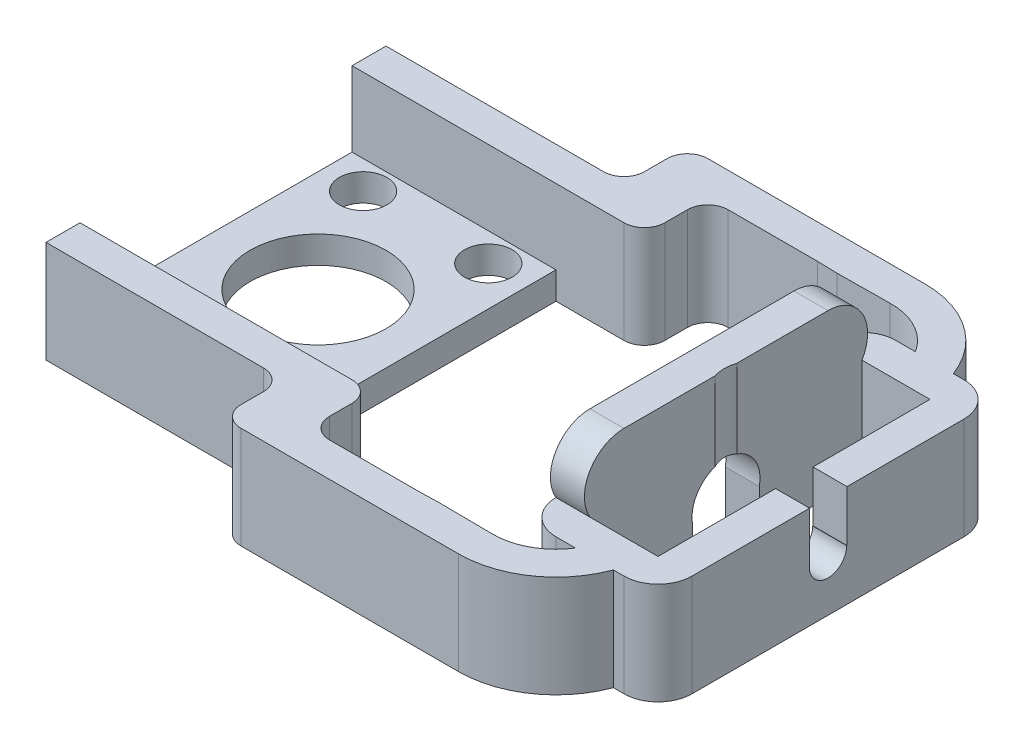
SolidWorks part; units mm, degrees
ref_plane "Front Plane" through (0, 0, 0) normal (0, 0, 1) x (1, 0, 0)
ref_plane "Top Plane" through (0, 0, 0) normal (0, 1, 0) x (1, 0, 0)
ref_plane "Right Plane" through (0, 0, 0) normal (1, 0, 0) x (0, 0, -1)
sketch "Sketch1" plane through (0, 0, 0) normal (0, 1, 0) x (1, 0, 0)
  line L11 (-45, 25) -> (45, 25)
  line L12 (-45, 25) -> (-45, -25)
  line L13 (-45, -25) -> (45, -25)
  line L14 (45, 25) -> (45, -25)
  line L15 (-45, 25) -> (45, -25) construction
  line L16 (-45, -25) -> (45, 25) construction
  point P0 (0, 0)
  dimension "D1" = 50
  dimension "D2" = 90
extrude "Boss-Extrude1" add sketch "Sketch1" along normal blind 15
sketch "Sketch2" plane through (0, 15, 0) normal (0, 1, 0) x (1, 0, 0)
  line L0 (45, -25) -> (45, 25) construction
  line L1 (-15, 20) -> (25, 20)
  line L2 (-15, 20) -> (-15, -20)
  line L3 (-15, -20) -> (25, -20)
  line L4 (25, 20) -> (25, -20)
  line L5 (-15, 20) -> (25, -20) construction
  line L6 (-15, -20) -> (25, 20) construction
  line L7 (30, 20) -> (40, 20)
  line L8 (30, 20) -> (30, -20)
  line L9 (30, -20) -> (40, -20)
  line L10 (40, 20) -> (40, -20)
  line L11 (30, 20) -> (40, -20) construction
  line L12 (30, -20) -> (40, 20) construction
  point P0 (5, 0)
  point P5 (35, 0)
  dimension "D1" = 5
  dimension "D2" = 5
  dimension "D4" = 10
  dimension "D5" = 40
extrude "Cut-Extrude1" cut sketch "Sketch2" against normal blind 15
sketch "Sketch5" plane through (45, 0, 0) normal (1, 0, 0) x (0, 0, -1)
  line L0 (0, 0) -> (0, 15) construction
  line L1 (-25, 0) -> (25, 0) construction
  line L2 (-25, 15) -> (25, 15) construction
  circle A0 centre (-9.038, 7.6891) radius 1.5
  circle A1 centre (9.038, 7.6891) radius 1.5
  point P8 (0, 7.5)
  dimension "D1" = 9.04
sketch "Sketch6" plane through (45, 0, 0) normal (1, 0, 0) x (0, 0, -1)
  line L0 (0, 0) -> (0, 15) construction
  line L1 (-25, 0) -> (25, 0) construction
  line L2 (-25, 15) -> (25, 15) construction
  circle A0 centre (0, 7.5) radius 2.75
  dimension "D1" = 5.5
extrude "Cut-Extrude4" cut sketch "Sketch6" against normal blind 7
sketch "Sketch8" plane through (25, 0, 0) normal (-1, 0, 0) x (0, 0, 1)
  line L0 (0, 0) -> (0, 15) construction
  line L1 (20, 0) -> (-20, 0) construction
  line L2 (20, 15) -> (-20, 15) construction
  circle A0 centre (0, 7.5) radius 5
  dimension "D1" = 10
extrude "Cut-Extrude5" cut sketch "Sketch8" against normal blind 7
sketch "Sketch9" plane through (45, 0, 0) normal (1, 0, 0) x (0, 0, -1)
  line L0 (0, 0) -> (0, 15) construction
  line L1 (-25, 0) -> (25, 0) construction
  line L2 (0, 7.5) -> (-9.04, 7.5) construction
  circle A0 centre (-9.04, 7.5) radius 1.5
  circle A1 centre (9.04, 7.5) radius 1.5
  dimension "D1" = 9.04
sketch "Sketch10" plane through (0, 15, 0) normal (0, 1, 0) x (1, 0, 0)
  line L0 (0, 0) -> (45, 0) construction
  line L1 (45, -25) -> (45, 25) construction
  line L2 (45, 25) -> (-45, 25) construction
  line L3 (11.5635, 25) -> (17.139, 25)
  line L4 (32.861, 25) -> (38.4365, 25)
  line L5 (11.5635, -25) -> (17.139, -25)
  line L6 (32.861, -25) -> (38.4365, -25)
  arc A0 (25, 34.3366) -> (38.4365, 25) centre (25, 20) cw
  arc A1 (25, 34.3366) -> (11.5635, 25) centre (25, 20) ccw
  arc A2 (25, 29.3164) -> (32.861, 25) centre (25, 20) cw
  arc A3 (25, 29.3164) -> (17.139, 25) centre (25, 20) ccw
  arc A4 (25, -29.3164) -> (17.139, -25) centre (25, -20) cw
  arc A5 (25, -29.3164) -> (32.861, -25) centre (25, -20) ccw
  arc A6 (25, -34.3366) -> (38.4365, -25) centre (25, -20) ccw
  arc A7 (25, -34.3366) -> (11.5635, -25) centre (25, -20) cw
extrude "Boss-Extrude2" add sketch "Sketch10" against normal blind 15
sketch "Sketch11" plane through (0, 15, 0) normal (0, 1, 0) x (1, 0, 0)
  line L0 (25, 20) -> (25, 25)
  line L1 (32.861, 25) -> (17.139, 25) construction
  line L2 (25, 25) -> (17.139, 25)
  line L3 (17.139, 25) -> (17.139, 20)
  line L4 (25, 20) -> (-15, 20) construction
  line L5 (17.139, 20) -> (25, 20)
  line L6 (0, 0) -> (30, 0) construction
  line L7 (30, 20) -> (30, -20) construction
  line L8 (17.139, -20) -> (25, -20)
  line L9 (25, -20) -> (25, -25)
  line L10 (25, -25) -> (17.139, -25)
  line L11 (17.139, -25) -> (17.139, -20)
extrude "Cut-Extrude7" cut sketch "Sketch11" against normal blind 15
fillet "Fillet1" radius 5 2 edges at (25, 7.5, -25) (25, 7.5, 25)
fillet "Fillet2" radius 5 2 edges at (17.139, 7.5, 20) (17.139, 7.5, -20)
fillet "Fillet3" radius 5 2 edges at (17.139, 7.5, 25) (17.139, 7.5, -25)
fillet "Fillet4" radius 5 2 edges at (45, 7.5, 25) (45, 7.5, -25)
fillet "Fillet5" radius 5 2 edges at (11.5635, 7.5, -25) (11.5635, 7.5, 25)
sketch "Sketch12" plane through (0, 15, 0) normal (0, 1, 0) x (1, 0, 0)
  line L1 (38.8459, 2.7908) -> (45.6477, 2.7908)
  line L2 (38.8459, 2.7908) -> (38.8459, -2.7092)
  line L3 (38.8459, -2.7092) -> (45.6477, -2.7092)
  line L4 (45.6477, 2.7908) -> (45.6477, -2.7092)
  line L5 (38.8459, 2.7908) -> (45.6477, -2.7092) construction
  line L6 (38.8459, -2.7092) -> (45.6477, 2.7908) construction
  point P0 (42.2468, 0.0408)
  dimension "D1" = 5.5
extrude "Cut-Extrude8" cut sketch "Sketch12" against normal blind 7.5
sketch "Sketch13" plane through (0, 0, 0) normal (0, -1, 0) x (1, 0, 0)
  line L1 (23.6838, 4.8946) -> (31.331, 4.8946)
  line L2 (23.6838, 4.8946) -> (23.6838, -4.8946)
  line L3 (23.6838, -4.8946) -> (31.331, -4.8946)
  line L4 (31.331, 4.8946) -> (31.331, -4.8946)
  line L5 (23.6838, 4.8946) -> (31.331, -4.8946) construction
  line L6 (23.6838, -4.8946) -> (31.331, 4.8946) construction
  point P0 (27.5074, 0)
extrude "Cut-Extrude9" cut sketch "Sketch13" against normal blind 7.5
sketch "Sketch15" plane through (30, 0, 0) normal (1, 0, 0) x (0, 0, -1)
  line L0 (0, 0) -> (0, 23.8085) construction
  line L1 (-15, 23.8085) -> (15, 23.8085)
  line L2 (-20, 15) -> (20, 15)
  arc A0 (-15, 23.8085) -> (-20, 15) centre (-15, 17.9851) ccw
  arc A1 (15, 23.8085) -> (20, 15) centre (15, 17.9851) cw
  point P6 (0, 23.8085)
extrude "Boss-Extrude4" add sketch "Sketch15" against normal blind 5
sketch "Sketch16" plane through (0, 15, 0) normal (0, 1, 0) x (1, 0, 0)
  line L0 (-15, -20) -> (-45, -20)
  line L1 (-45, 25) -> (-45, -25) construction
  line L2 (-15, 20) -> (-45, 20)
  line L3 (-45, 20) -> (-45, -20)
  line L4 (-15, -20) -> (-15, 20)
extrude "Cut-Extrude10" cut sketch "Sketch16" against normal blind 5
sketch "Sketch17" plane through (0, 23.8085, 0) normal (0, 1, 0) x (1, 0, 0)
  line L0 (25, 0) -> (45, 0) construction
  line L1 (25, 15) -> (25, -15) construction
  line L2 (45, -2.75) -> (45, 2.75) construction
  circle A0 centre (35, 0) radius 5.25
  dimension "D1" = 10.5
sketch "Sketch18" plane through (0, 10, 0) normal (0, 1, 0) x (1, 0, 0)
  line L0 (-15, 0) -> (-45, 0) construction
  line L1 (-15, -20) -> (-15, 20) construction
  line L2 (-45, 20) -> (-45, -20) construction
  line L3 (-30, -20) -> (-30, 20) construction
  line L4 (-45, -20) -> (-15, -20) construction
  line L5 (-15, 20) -> (-45, 20) construction
  circle A0 centre (-30, 0) radius 10
  circle A1 centre (-39.207, 15.8414) radius 3.5
  circle A2 centre (-20.793, 15.8414) radius 3.5
  circle A3 centre (-20.793, -15.8414) radius 3.5
  circle A4 centre (-39.207, -15.8414) radius 3.5
extrude "Cut-Extrude12" cut sketch "Sketch18" against normal blind 11
extrude "Cut-Extrude13" cut sketch "Sketch17" against normal blind 32 contours A0
sketch "Sketch19" plane through (0, 15, 0) normal (0, 1, 0) x (1, 0, 0)
  line L0 (25, 34.3366) -> (-10, 34.3366)
  line L1 (-10, 34.3366) -> (-10, 25)
  line L2 (8.4499, 25) -> (-45, 25) construction
  line L3 (25, 29.3164) -> (-2, 29.3164)
  line L4 (-2, 29.3164) -> (-2, 25)
  line L5 (43.7002, 0) -> (-45, 0) construction
  line L6 (-45, 20) -> (-45, -20) construction
  line L7 (-10, 25) -> (-2, 25)
  line L8 (25, 34.3366) -> (25, 29.3164)
  line L9 (-2, -29.3164) -> (-2, -25)
  line L10 (-10, -25) -> (-2, -25)
  line L11 (-10, -34.3366) -> (-10, -25)
  line L12 (25, -34.3366) -> (25, -29.3164)
  line L13 (25, -34.3366) -> (-10, -34.3366)
  line L14 (25, -29.3164) -> (-2, -29.3164)
  arc A0 (38.4365, 25) -> (12.7294, 27.4142) centre (25, 20) ccw construction
  arc A1 (32.861, 25) -> (18.4113, 26.5867) centre (25, 20) ccw construction
  arc A2 (32.861, 25) -> (18.4113, 26.5867) centre (25, 20) ccw construction
  point P21 (0, 0)
  point P22 (0, 0)
  dimension "D1" = 35
  dimension "D2" = 27
extrude "Boss-Extrude5" add sketch "Sketch19" against normal blind 15
sketch "Sketch20" plane through (0, 15, 0) normal (0, 1, 0) x (1, 0, 0)
  line L0 (-2, -25) -> (-2, -20)
  line L1 (-45, -20) -> (12.139, -20) construction
  line L2 (-2, -20) -> (17.115, -20)
  line L4 (17.115, -29.2413) -> (14.103, -29.3164)
  line L5 (14.103, -29.3164) -> (-2, -25)
  line L6 (17.115, -29.2413) -> (25, -29.3164)
  line L7 (25, -29.3164) -> (17.115, -20)
  line L8 (44.5665, 0) -> (-6.9443, 0) construction
  line L9 (17.115, 29.2413) -> (14.103, 29.3164)
  line L10 (17.115, 29.2413) -> (25, 29.3164)
  line L11 (25, 29.3164) -> (17.115, 20)
  line L12 (-2, 20) -> (17.115, 20)
  line L13 (-2, 25) -> (-2, 20)
  line L14 (14.103, 29.3164) -> (-2, 25)
  arc A0 (18.4113, -26.5867) -> (32.861, -25) centre (25, -20) ccw construction
extrude "Cut-Extrude14" cut sketch "Sketch20" against normal blind 15
fillet "Fillet7" radius 3 8 edges at (-10, 7.5, -34.3366) (-10, 7.5, -25) (-10, 7.5, 34.3366) (-10, 7.5, 25) (-2, 7.5, 29.3164) (-2, 7.5, 20) (-2, 7.5, -20) (-2, 7.5, -29.3164)
sketch "Sketch21" plane through (-45, 0, 0) normal (-1, 0, 0) x (0, 0, 1)
  line L0 (-20, 10) -> (-20, 4)
  line L1 (-20, 10) -> (20, 10)
  line L2 (20, 10) -> (20, 4)
  line L3 (20, 4) -> (-20, 4)
  dimension "D1" = 6
extrude "Cut-Extrude15" cut sketch "Sketch21" against normal blind 30
